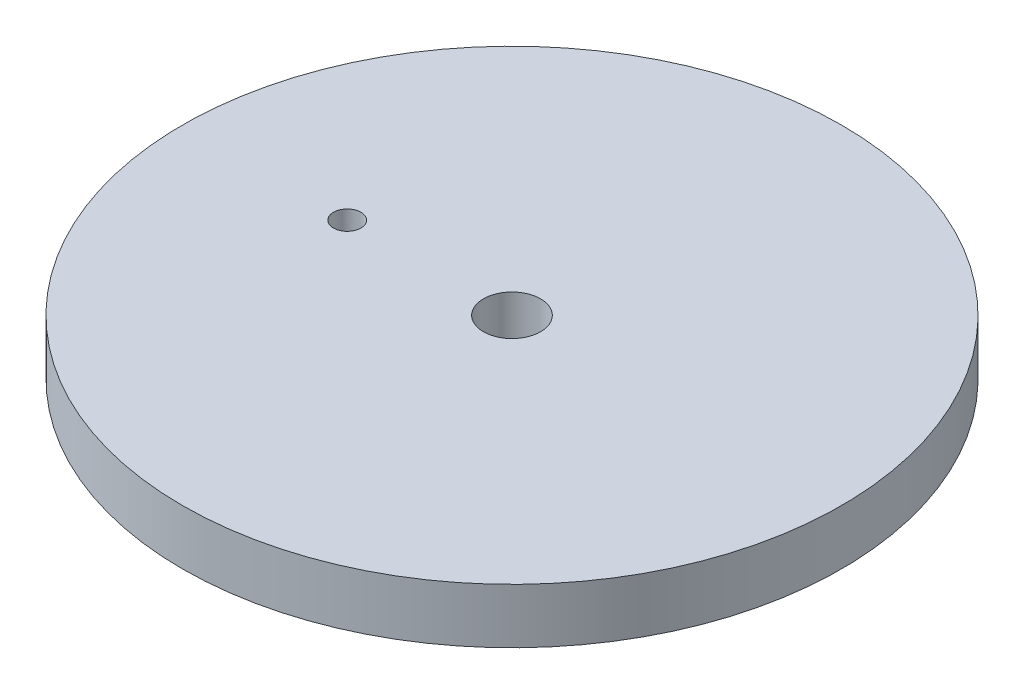
SolidWorks part; units mm, degrees
material "G10 Fiberglass"
ref_plane "Front Plane" through (0, 0, 0) normal (0, 0, 1) x (1, 0, 0)
ref_plane "Top Plane" through (0, 0, 0) normal (0, 1, 0) x (1, 0, 0)
ref_plane "Right Plane" through (0, 0, 0) normal (1, 0, 0) x (0, 0, -1)
sketch "Sketch1" plane through (0, 0, 0) normal (0, 1, 0) x (1, 0, 0)
  circle A0 centre (0, 0) radius 38.1
  circle A1 centre (0, 0) radius 3.302
  circle A2 centre (-19.05, 0) radius 1.5875
  dimension "D1" = 76.2
  dimension "D2" = 6.604
  dimension "D3" = 3.175
  dimension "D4" = 19.05
extrude "Boss-Extrude1" add sketch "Sketch1" along normal blind 6.35
ref_axis "Axis1" through (0, -0.3175, 0) along (0, 1, 0)
